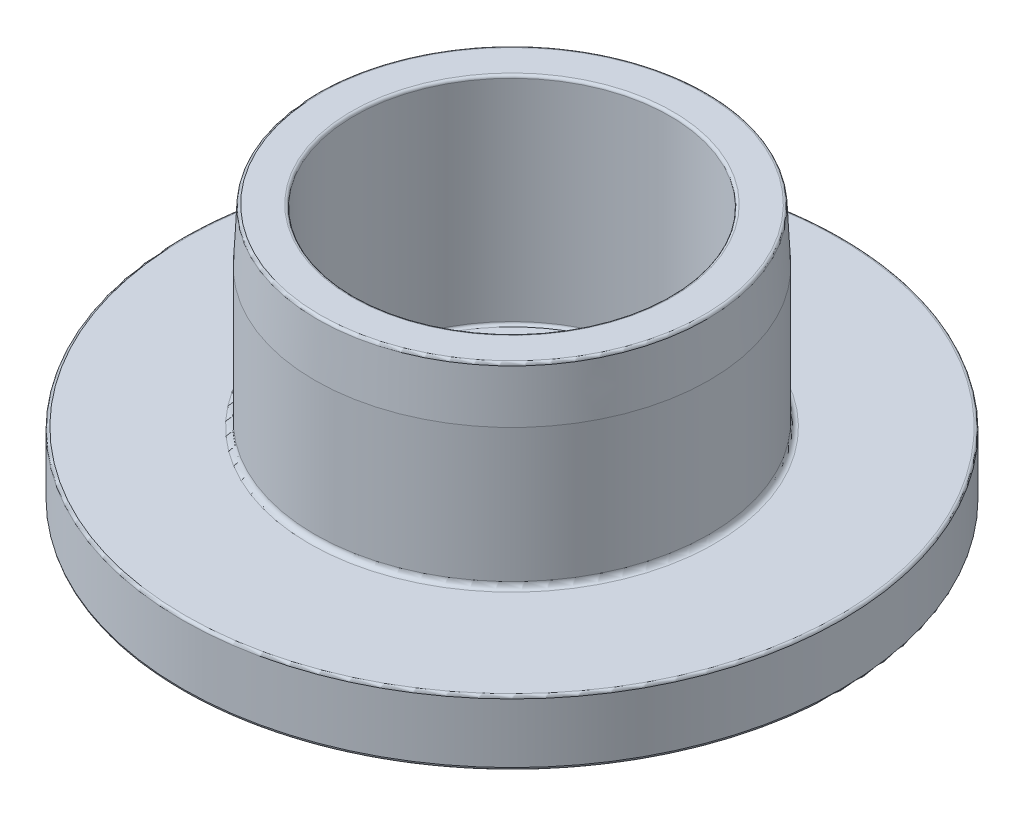
SolidWorks part; units mm, degrees
ref_plane "Plano frontal" through (0, 0, 0) normal (0, 0, 1) x (1, 0, 0)
ref_plane "Plano superior" through (0, 0, 0) normal (0, 1, 0) x (1, 0, 0)
ref_plane "Plano direito" through (0, 0, 0) normal (1, 0, 0) x (0, 0, -1)
sketch "Esboço1" plane through (0, 0, 0) normal (0, 0, 1) x (1, 0, 0)
  line L0 (0, -52.5162) -> (0, 53.8129) construction
  line L1 (29.25, 49.9228) -> (36, 49.9228)
  line L2 (36, 49.9228) -> (36.5, 39.9228)
  line L3 (36.5, 39.9228) -> (36.5, 14.2228)
  line L4 (36.5, 14.2228) -> (61, 14.2228)
  line L5 (61, 14.2228) -> (61, 2.2228)
  line L6 (61, 2.2228) -> (33, 2.2228)
  line L7 (33, 2.2228) -> (33, -5.2772)
  line L8 (33, -5.2772) -> (32, -5.2772)
  line L9 (32, -5.2772) -> (30.75, -17.7772)
  line L10 (30.75, -17.7772) -> (23.5, -17.7772)
  line L11 (23.5, -17.7772) -> (23.5, 9.9228)
  line L12 (23.5, 9.9228) -> (29.25, 9.9228)
  line L13 (29.25, 9.9228) -> (29.25, 49.9228)
  dimension "D1" = 29.25
  dimension "D2" = 36
  dimension "D3" = 36.5
  dimension "D4" = 35.7
  dimension "D5" = 12
  dimension "D6" = 7.5
  dimension "D7" = 20
  dimension "D8" = 12.5
  dimension "D9" = 23.5
  dimension "D10" = 40
  dimension "D11" = 10
  dimension "D12" = 61
  dimension "D13" = 30.75
  dimension "D14" = 32
  dimension "D15" = 33
revolve "Revolução1" add sketch "Esboço1" angle 360 about L0
fillet "Filete1" radius 0.5 4 edges at (0, 2.2228, -61) (0, 14.2228, -61) (0, 49.9228, -29.25) (0, 49.9228, -36)
fillet "Filete2" radius 1 1 edges at (0, 14.2228, -36.5)
chamfer "Chanfro1" distance 1 angle 30 1 edges at (0, 9.9228, -23.5) first distance on face at (0, 9.9228, -23.5)
fillet "Filete3" radius 0.5 1 edges at (0, 9.9228, -29.25)
fillet "Filete4" radius 1.5 1 edges at (0, -5.2772, -32)
fillet "Filete5" radius 0.5 2 edges at (0, -17.7772, -23.5) (0, -17.7772, -30.75)
fillet "Filete6" radius 1 1 edges at (0, 2.2228, -33)
